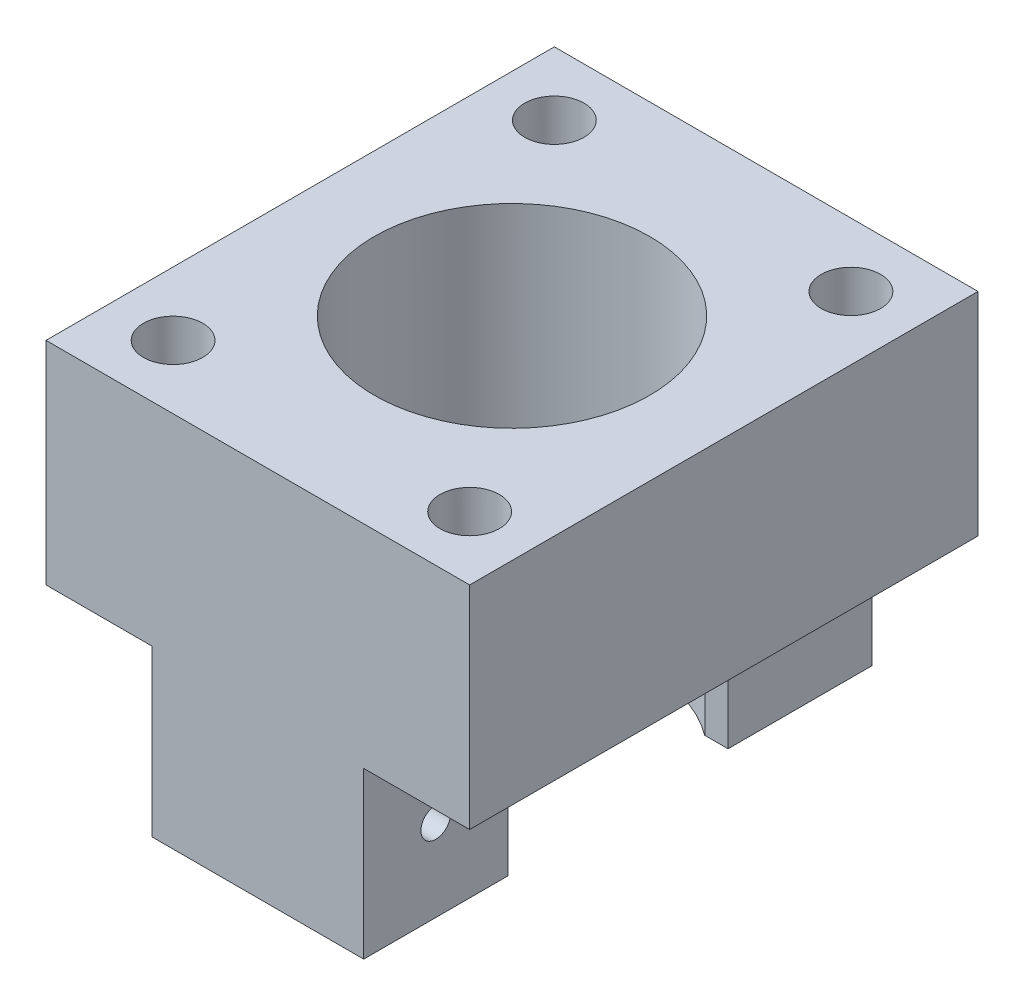
SolidWorks part; units mm, degrees
ref_plane "前视基准面" through (0, 0, 0) normal (0, 0, 1) x (1, 0, 0)
ref_plane "上视基准面" through (0, 0, 0) normal (0, 1, 0) x (1, 0, 0)
ref_plane "右视基准面" through (0, 0, 0) normal (1, 0, 0) x (0, 0, -1)
other "Configuration Table"
sketch "草图1" plane through (0, 0, 0) normal (0, 1, 0) x (1, 0, 0)
  line L1 (0, 0) -> (10, 0)
  line L2 (0, 0) -> (0, -12)
  line L3 (0, -12) -> (10, -12)
  line L4 (10, 0) -> (10, -12)
  dimension "D4" = 10
  dimension "D11" = 12
extrude "凸台-拉伸1" add sketch "草图1" along normal blind 5
sketch "草图2" plane through (0, 0, 0) normal (0, -1, 0) x (1, 0, 0)
  line L0 (0, 12) -> (10, 0)
  circle A0 centre (1.5, 1.5) radius 0.7
  circle A1 centre (1.5, 10.5) radius 0.7
  circle A2 centre (8.5, 10.5) radius 0.7
  circle A3 centre (8.5, 1.5) radius 0.7
  circle A16 centre (5, 6) radius 3.25
  circle A17 centre (1.5, 10.5) radius 1
  circle A18 centre (8.5, 10.5) radius 1
  circle A19 centre (8.5, 1.5) radius 1
  circle A20 centre (1.5, 1.5) radius 1
  dimension "D1" = 1.4
  dimension "D2" = 6.5
  dimension "D3" = 2
extrude "切除-拉伸1" cut sketch "草图2" against normal through all contours A0 | A3 | A2 | A1
extrude "切除-拉伸2" cut sketch "草图2<3>" against normal through all contours A16
sketch "草图2<3>" plane through (0, 0, 0) normal (0, -1, 0) x (1, 0, 0) same geometry as "草图2"
extrude "切除-拉伸3" cut sketch "草图2<4>" against normal offset from surface (3 mm away) 2 contours A17 | A18 | A19 | A20 up to face at (5, 5, 2.75)
sketch "草图2<4>" plane through (0, 0, 0) normal (0, -1, 0) x (1, 0, 0) same geometry as "草图2"
sketch "草图3" plane through (0, 0, 0) normal (0, -1, 0) x (1, 0, 0)
  line L0 (10, 0) -> (0, 0) construction
  line L1 (2.5, 0) -> (7.5, 0)
  line L2 (2.5, 0) -> (2.5, 3.4)
  line L3 (2.5, 3.4) -> (7.5, 3.4)
  line L4 (7.5, 0) -> (7.5, 3.4)
  line L5 (0, 12) -> (10, 12) construction
  line L6 (2.5, 12) -> (7.5, 12)
  line L7 (2.5, 12) -> (2.5, 8.6)
  line L8 (2.5, 8.6) -> (7.5, 8.6)
  line L9 (7.5, 12) -> (7.5, 8.6)
  line L10 (0, 0) -> (0, 12) construction
  circle A0 centre (1.5, 10.5) radius 1 construction
  circle A1 centre (8.5, 10.5) radius 1 construction
  circle A2 centre (5, 6) radius 3.25 construction
  circle A3 centre (5, 6) radius 3.25
  circle M13 centre (5, 6) radius 3.25
  line M15 (0, 0) -> (10, 0)
  line M17 (10, 12) -> (0, 12)
  dimension "D1" = 3.4
  dimension "D2" = 3.4
extrude "凸台-拉伸2" add sketch "草图3" along normal blind 3.9 contours L9 L7 L8 M17 M13 | L4 L3 L2 M15 M13 region at (5, 0, 1.5374) region at (5, 0, 10.4626)
sketch "草图4" plane through (2.5, 0, 0) normal (-1, 0, 0) x (0, 0, 1)
  line L0 (0, 0) -> (3.4, -3.9)
  line L1 (12, 0) -> (8.6, -3.9)
  circle A0 centre (10.3, -1.95) radius 0.35
  circle A1 centre (1.7, -1.95) radius 0.35
  point P12 (0, 0)
  point P13 (0, 0)
  dimension "D1" = 0.7
extrude "切除-拉伸4" cut sketch "草图4" against normal through all contours A1 | A0
